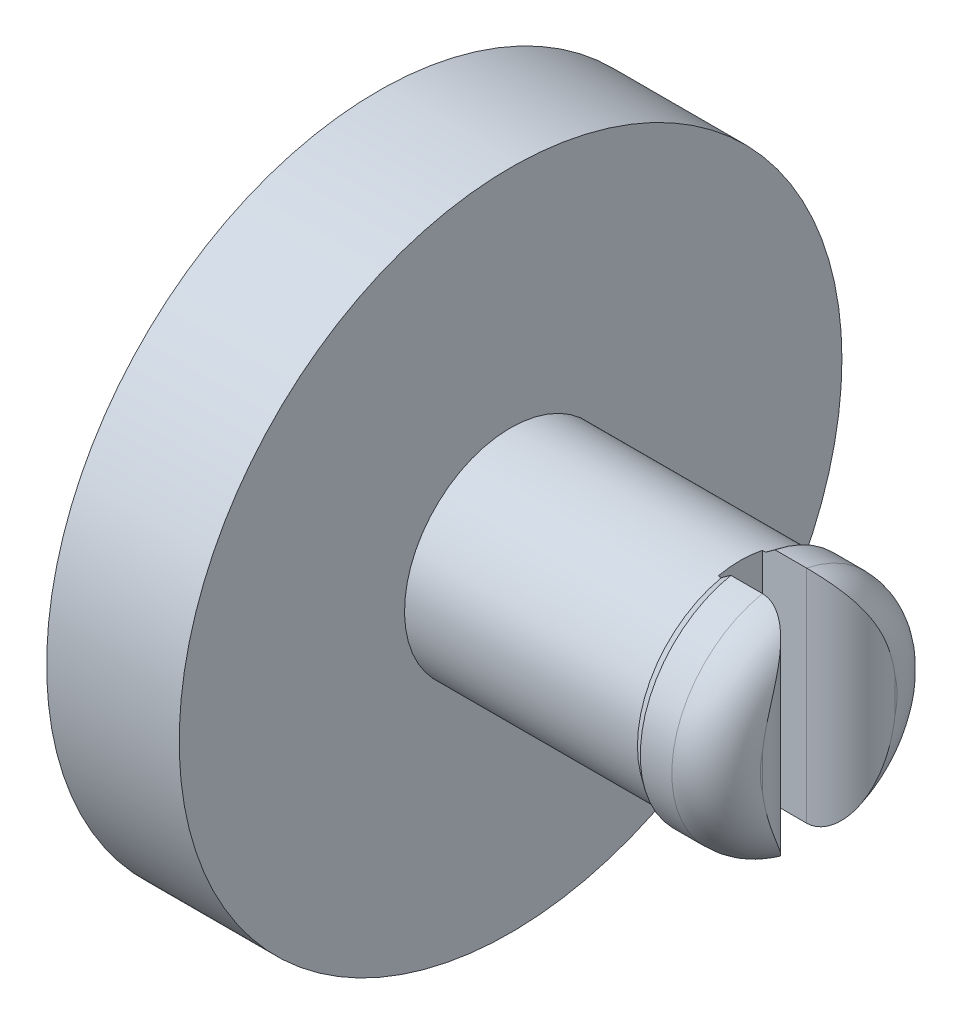
SolidWorks part; units mm, degrees
ref_plane "Front Plane" through (0, 0, 0) normal (1, 0, 0) x (0, 1, 0)
ref_plane "Top Plane" through (0, 0, 0) normal (0, 0, 1) x (0, 1, 0)
ref_plane "Right Plane" through (0, 0, 0) normal (0, 1, 0) x (-1, 0, 0)
sketch "Sketch1" plane through (0, 0, 0) normal (1, 0, 0) x (0, 1, 0)
  circle A0 centre (0, 0) radius 7.5
  dimension "D1" = 15
extrude "Boss-Extrude1" add sketch "Sketch1" along normal blind 3
sketch "Sketch2" plane through (3, 0, 0) normal (1, 0, 0) x (0, 0, -1)
  circle A0 centre (0, 0) radius 2.4
  dimension "D1" = 4.8
extrude "Boss-Extrude2" add sketch "Sketch2" along normal blind 5.2
sketch "Sketch3" plane through (8.2, 0, 0) normal (1, 0, 0) x (0, 1, 0)
  line L0 (-2.5005, 0.5) -> (2.5005, 0.5)
  line L1 (2.5005, -0.5) -> (-2.5005, -0.5)
  arc A0 (-2.5005, -0.5) -> (2.5005, -0.5) centre (0, 0) ccw
  arc A1 (2.5005, 0.5) -> (-2.5005, 0.5) centre (0, 0) ccw
  dimension "D1" = 5.1
  dimension "D2" = 1
extrude "Boss-Extrude3" add sketch "Sketch3" along normal blind 2
fillet "Fillet1" radius 1 2 edges at (10.2, 0, 0.5) (10.2, 0, 2.55)
fillet "Fillet2" radius 1 2 edges at (10.2, 0, -0.5) (10.2, 0, -2.55)
chamfer "Chamfer2" distance 0.2 angle 55 2 edges at (8.2, 0, -2.55) (8.2, 0, 2.55) first distance on face at (8.2, 0, -1.4875) first distance on face at (8.2, 0, 1.4875)
